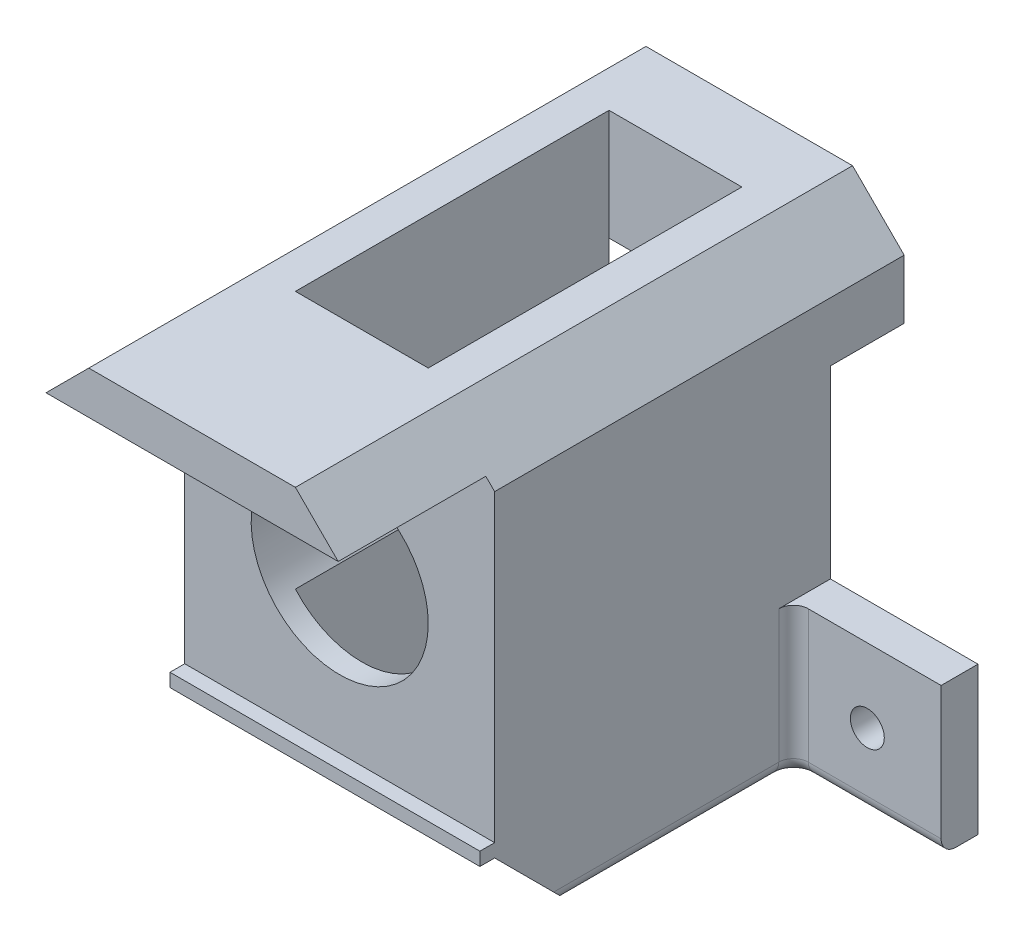
SolidWorks part; units mm, degrees
ref_plane "정면" through (0, 0, 0) normal (0, 0, 1) x (1, 0, 0)
ref_plane "윗면" through (0, 0, 0) normal (0, 1, 0) x (1, 0, 0)
ref_plane "우측면" through (0, 0, 0) normal (1, 0, 0) x (0, 0, -1)
sketch "스케치1" plane through (0, 0, 0) normal (0, 0, 1) x (1, 0, 0)
  line L1 (-9, 0) -> (-21, 0)
  line L2 (-9, 0) -> (-9, 60)
  line L3 (-9, 60) -> (-21, 60)
  line L4 (-21, 0) -> (-21, 60)
  line L5 (9, 0) -> (21, 0)
  line L6 (9, 0) -> (9, 60)
  line L7 (9, 60) -> (21, 60)
  line L8 (21, 0) -> (21, 60)
  dimension "D1" = 0
  dimension "D2" = 12
  dimension "D3" = 12
  dimension "D4" = 9
  dimension "D5" = 9
  dimension "D6" = 60
  dimension "D7" = 60
extrude "보스-돌출1" add sketch "스케치1" along normal blind 42.5
sketch "스케치2" plane through (0, 0, 42.5) normal (0, 0, 1) x (1, 0, 0)
  line L1 (21, 0) -> (-21, 0)
  line L2 (21, 0) -> (21, 60)
  line L3 (21, 60) -> (-21, 60)
  line L4 (-21, 0) -> (-21, 60)
  circle A0 centre (0, 33) radius 12
  dimension "D1" = 24
  dimension "D2" = 27
  dimension "D3" = 0
extrude "보스-돌출2" add sketch "스케치2" along normal blind 3
sketch "스케치3" plane through (0, 0, 45.5) normal (0, 0, 1) x (1, 0, 0)
  circle A0 centre (0, 33) radius 12
  circle A1 centre (0, 33) radius 12 construction
  dimension "D1" = 0
extrude "컷-돌출1" cut sketch "스케치3" against normal through all
sketch "스케치4" plane through (0, 0, 0) normal (0, 0, -1) x (-1, 0, 0)
  line L0 (21, 60) -> (21, 0) construction
  line L1 (-21, 60) -> (21, 60)
  line L2 (-21, 60) -> (-21, 45)
  line L3 (-21, 45) -> (21, 45)
  line L4 (21, 60) -> (21, 45)
  dimension "D1" = 15
extrude "보스-돌출3" add sketch "스케치4" along normal blind 10
chamfer "모따기1" distance 10 angle 45 1 edges at (0, 0, 45.5)
sketch "스케치5" plane through (21, 0, 0) normal (1, 0, 0) x (0, 0, -1)
  line L1 (0, 0) -> (-5, 0)
  line L2 (0, 0) -> (0, 20)
  line L3 (0, 20) -> (-5, 20)
  line L4 (-5, 0) -> (-5, 20)
  dimension "D1" = 20
  dimension "D2" = 5
extrude "보스-돌출4" add sketch "스케치5" along normal blind 20
hole_wizard "M4 여유 구멍1" positions "스케치6" profile "스케치7" hole size "M4" standard "KS" end condition through all
sketch "스케치6" plane through (0, 0, 5) normal (0, 0, 1) x (1, 0, 0)
  line L0 (41, 20) -> (21, 20) construction
  line L1 (41, 20) -> (41, 0) construction
  point P0 (31, 10)
  dimension "D1" = 10
  dimension "D2" = 10
sketch "스케치7" plane through (31, 10, 5) normal (1, 0, 0) x (0, -1, 0)
  line L0 (0, 0) -> (0, 15)
  line L1 (0, 15) -> (2.3, 15)
  line L2 (2.3, 15) -> (2.3, 0)
  line L5 (2.3, 0) -> (0, 0)
  line L11 (0, -6.35) -> (0, 107.95) construction
  dimension "관통 구멍 지름" = 4.6
  dimension "관통 구멍 깊이" = 15
mirror "대칭 복사1" about plane through (0, 0, 0) normal (1, 0, 0) of "M4 여유 구멍1", "보스-돌출4"
fillet "필렛1" radius 2 6 edges at (-31, 0, 5) (31, 0, 5) (-21, 0, 20.25) (21, 0, 20.25) (21, 10, 5) (-21, 10, 5)
chamfer "모따기2" distance 7 angle 45 2 edges at (-21, 60, 17.75) (21, 60, 17.75)
sketch "스케치8" plane through (0, 0, 45.5) normal (0, 0, 1) x (1, 0, 0)
  line L0 (-19.8, 54.2) -> (19.8, 54.2)
  line L1 (-14, 60) -> (-21, 53) construction
  line L2 (21, 53) -> (14, 60) construction
  line L3 (19.8, 54.2) -> (14, 60)
  line L4 (14, 60) -> (-14, 60)
  line L5 (14, 60) -> (-14, 60) construction
  line L6 (-14, 60) -> (-19.8, 54.2)
  dimension "D1" = 5.8
extrude "보스-돌출5" add sketch "스케치8" along normal blind 20
sketch "스케치9" plane through (0, 0, 45.5) normal (0, 0, 1) x (1, 0, 0)
  line L0 (21, 10) -> (21, 53) construction
  line L1 (-21, 10) -> (21, 10)
  line L2 (-21, 10) -> (-21, 11.8)
  line L3 (-21, 11.8) -> (21, 11.8)
  line L4 (21, 10) -> (21, 11.8)
  dimension "D1" = 1.8
extrude "보스-돌출6" add sketch "스케치9" along normal blind 2
